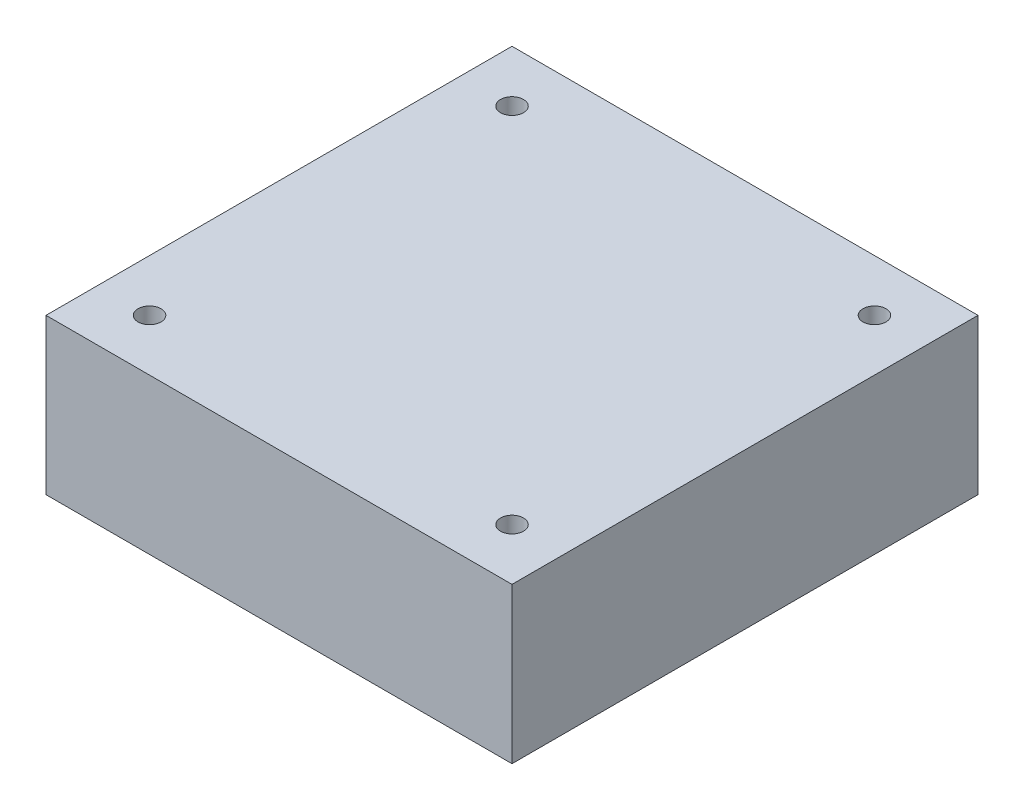
SolidWorks part; units mm, degrees
ref_plane "Front" through (0, 0, 0) normal (0, 0, 1) x (1, 0, 0)
ref_plane "Top" through (0, 0, 0) normal (0, 1, 0) x (1, 0, 0)
ref_plane "Right" through (0, 0, 0) normal (1, 0, 0) x (0, 0, -1)
sketch "Sketch11" plane through (0, 0, 0) normal (0, 1, 0) x (1, 0, 0)
  line L1 (-40.5, -40.5) -> (40.5, -40.5)
  line L2 (-40.5, -40.5) -> (-40.5, 40.5)
  line L3 (-40.5, 40.5) -> (40.5, 40.5)
  line L4 (40.5, -40.5) -> (40.5, 40.5)
  line L5 (-40.5, -40.5) -> (40.5, 40.5) construction
  line L6 (-40.5, 40.5) -> (40.5, -40.5) construction
  point P0 (0, 0)
  dimension "D1" = 81
extrude "Boss-Extrude1" add sketch "Sketch11" along normal blind 27
sketch "Sketch1" plane through (0, 0, 0) normal (0, 0, 1) x (1, 0, 0)
  line L0 (0, 25) -> (0, 10)
  line L1 (31.5, 19.8898) -> (31.5, -17.8473) construction
  line L2 (0, 0) -> (31.5, 0) construction
  line L3 (0, 25) -> (0, 0) construction
  line L4 (31.5, 0) -> (30.5, 0) construction
  line L5 (0, 10) -> (0, -10)
  line L6 (0, -10) -> (31.5, -10)
  line L7 (31.5, -10) -> (31.5, 0)
  spline S0 degree 3 poles (0, 25) (1.3715, 25) (4.0902, 24.3027) (10.7515, 17.1368) (25.5788, 15.0702) (31.0385, 6.4502) (31.5, 0) knots 0 0 0 0 0.091246 0.195023 0.675457 1 1 1 1
  spline S1 degree 3 poles (30.5, 0) (24.4624, 10.5881) (11.1572, 9.4928) (0, 10) knots 0 0 0 0 1 1 1 1 construction
  dimension "D1" = 25
  dimension "D4" = 31.5
  dimension "D5" = 20
  dimension "D2" = 1
  dimension "D3" = 15
revolve "Cut-Revolve1" cut sketch "Sketch1" angle 360 about L5
sketch "Sketch12" plane through (0, 0, 0) normal (0, -1, 0) x (1, 0, 0)
  line L0 (-40.5, 40.5) -> (40.5, 40.5) construction
  line L1 (-40.5, -40.5) -> (-40.5, 40.5) construction
  line L2 (0, 0) -> (0, 40.5) construction
  line L3 (0, 0) -> (-40.5, 0) construction
  circle A0 centre (-31.5, 31.5) radius 2
  circle A1 centre (31.5, 31.5) radius 2
  circle A2 centre (31.5, -31.5) radius 2
  circle A3 centre (-31.5, -31.5) radius 2
  dimension "D1" = 4
  dimension "D2" = 9
  dimension "D3" = 9
extrude "Cut-Extrude1" cut sketch "Sketch12" against normal through all
equation "\"CutAngle\"= 2"
